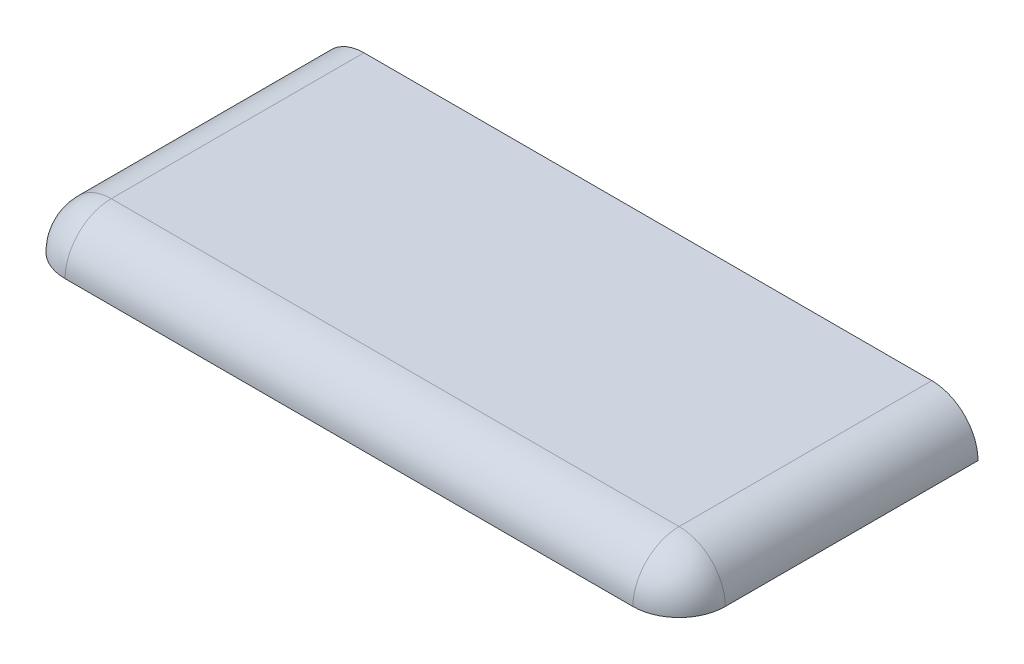
SolidWorks part; units mm, degrees
ref_plane "Front Plane" through (0, 0, 0) normal (0, 0, 1) x (1, 0, 0)
ref_plane "Top Plane" through (0, 0, 0) normal (0, 1, 0) x (1, 0, 0)
ref_plane "Right Plane" through (0, 0, 0) normal (1, 0, 0) x (0, 0, -1)
sketch "Sketch1" plane through (0, 0, 0) normal (0, 1, 0) x (1, 0, 0)
  line L1 (18.1553, -8.219) -> (-18.1553, -8.219)
  line L2 (18.1553, -8.219) -> (18.1553, 8.219)
  line L3 (18.1553, 8.219) -> (-18.1553, 8.219)
  line L4 (-18.1553, -8.219) -> (-18.1553, 8.219)
  line L5 (18.1553, -8.219) -> (-18.1553, 8.219) construction
  line L6 (18.1553, 8.219) -> (-18.1553, -8.219) construction
  point P0 (0, 0)
extrude "Boss-Extrude1" add sketch "Sketch1" along normal blind 2.54
fillet "Fillet1" radius 2.54 3 edges at (0, 2.54, 8.219) (18.1553, 1.27, 8.219) (-18.1553, 1.27, 8.219)
fillet "Fillet2" radius 2.54 4 edges at (-17.4114, 1.7961, 7.475) (17.4114, 1.7961, 7.475) (-18.1553, 2.54, -1.27) (18.1553, 2.54, -1.27)
sketch "Orientation Sketch" plane through (0, 0, -8.219) normal (0, 0, -1) x (-1, 0, 0)
  line L0 (-18.1553, 0) -> (18.1553, 0) construction
  line L1 (-15.6153, 2.54) -> (15.6153, 2.54) construction
  line L2 (-18.1553, 0) -> (18.1553, 0)
  line L3 (-15.6153, 2.54) -> (15.6153, 2.54)
  arc A0 (18.1553, 0) -> (15.6153, 2.54) centre (15.6153, 0) ccw construction
  arc A1 (-15.6153, 2.54) -> (-18.1553, 0) centre (-15.6153, 0) ccw construction
  arc A2 (18.1553, 0) -> (15.6153, 2.54) centre (15.6153, 0) ccw
  arc A3 (-15.6153, 2.54) -> (-18.1553, 0) centre (-15.6153, 0) ccw
  point P3 (0, 1.27)
other "FormTool1"
